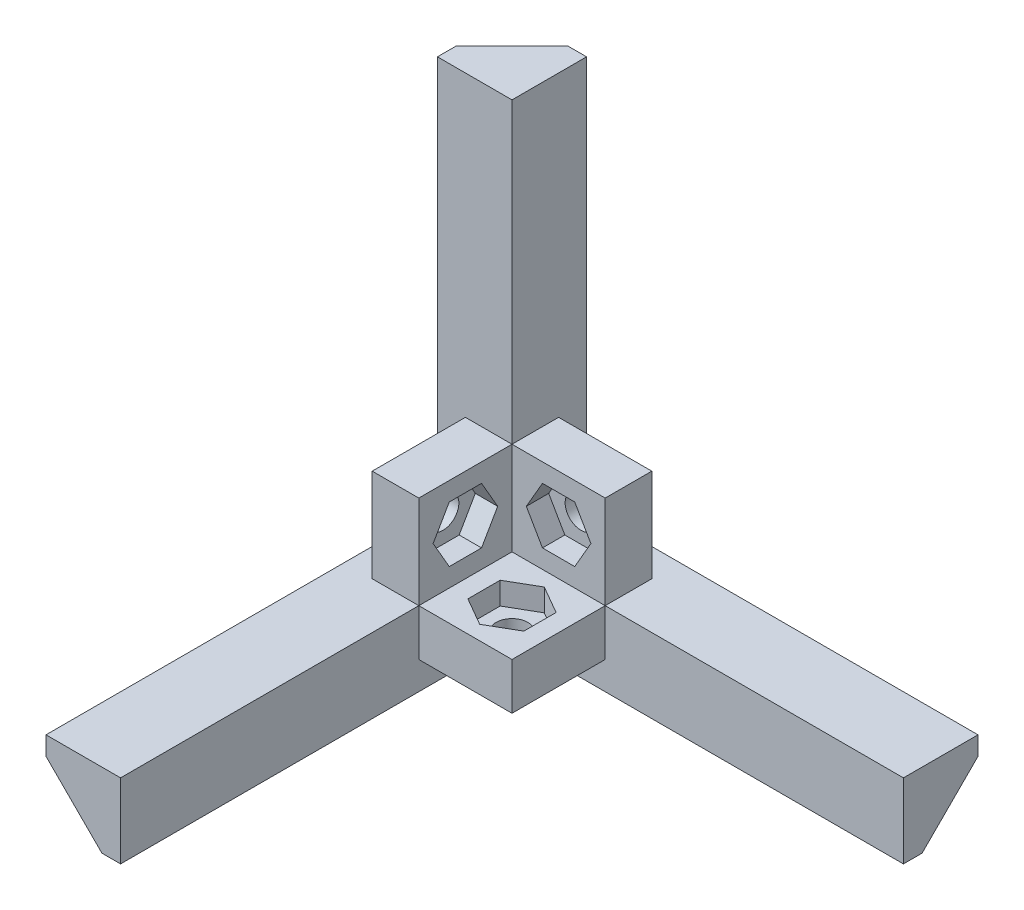
SolidWorks part; units mm, degrees
ref_plane "Piano frontale" through (0, 0, 0) normal (0, 0, 1) x (1, 0, 0)
ref_plane "Piano superiore" through (0, 0, 0) normal (0, 1, 0) x (1, 0, 0)
ref_plane "Piano destro" through (0, 0, 0) normal (1, 0, 0) x (0, 0, -1)
sketch "Sketch1" plane through (0, 0, 0) normal (0, 0, 1) x (1, 0, 0)
  line L0 (0, 0) -> (0, 42)
  line L1 (0, 42) -> (-8, 42)
  line L2 (-8, 42) -> (-8, -8)
  line L3 (-8, -8) -> (42, -8)
  line L4 (42, -8) -> (42, 0)
  line L5 (42, 0) -> (0, 0)
  dimension "D1" = 50
  dimension "D2" = 8
extrude "Boss-Extrude1" add sketch "Sketch1" along normal blind 8
sketch "Sketch2" plane through (0, 0, 8) normal (0, 0, 1) x (1, 0, 0)
  line L0 (0, 0) -> (-8, 0)
  line L1 (-8, 42) -> (-8, -8) construction
  line L2 (-8, 0) -> (-8, -8)
  line L3 (-8, -8) -> (0, -8)
  line L4 (-8, -8) -> (42, -8) construction
  line L5 (0, -8) -> (0, 0)
extrude "Boss-Extrude2" add sketch "Sketch2" along normal blind 42
sketch "Sketch3" plane through (0, 0, 8) normal (0, 0, 1) x (1, 0, 0)
  line L0 (0, 0) -> (10, 0)
  line L1 (42, 0) -> (0, 0) construction
  line L2 (10, 0) -> (10, -5)
  line L3 (10, -5) -> (0, -5)
  line L4 (0, -8) -> (0, 0) construction
  line L5 (0, -5) -> (0, 0)
  dimension "D1" = 5
  dimension "D2" = 10
extrude "Boss-Extrude3" add sketch "Sketch3" along normal blind 10
sketch "Sketch4" plane through (0, -5, 0) normal (0, -1, 0) x (1, 0, 0)
  line L0 (0, 18) -> (10, 18) construction
  line L1 (10, 18) -> (10, 8) construction
  circle A0 centre (5, 13) radius 1.7
  point P5 (5, 18)
  point P9 (10, 13)
  dimension "D1" = 3.4
extrude "Cut-Extrude1" cut sketch "Sketch4" against normal up to next
sketch "Sketch5" plane through (0, 0, 0) normal (0, 1, 0) x (1, 0, 0)
  line L1 (8.4641, -13) -> (6.7321, -10)
  line L2 (6.7321, -10) -> (3.2679, -10)
  line L3 (3.2679, -10) -> (1.5359, -13)
  line L4 (1.5359, -13) -> (3.2679, -16)
  line L5 (3.2679, -16) -> (6.7321, -16)
  line L6 (6.7321, -16) -> (8.4641, -13)
  circle A0 centre (5, -13) radius 3 construction
  dimension "D1" = 6
extrude "Cut-Extrude2" cut sketch "Sketch5" against normal blind 2.4
ref_plane "Plane1" through (0, -4, 4) normal (0, 0.7071, -0.7071) x (-1, 0, 0)
mirror "Mirror1" about plane through (0, -4, 4) normal (0, 0.7071, -0.7071) of "Cut-Extrude2", "Cut-Extrude1", "Boss-Extrude3"
chamfer "Chamfer1" distance 6 angle 45 3 edges at (-8, 17, 0) (-8, -8, 25) (17, -8, 0)
ref_plane "Plane2" through (-4, 0, 4) normal (0.7071, 0, -0.7071) x (0, 1, 0)
mirror "Mirror2" about plane through (-4, 0, 4) normal (0.7071, 0, -0.7071) of "Mirror1"
